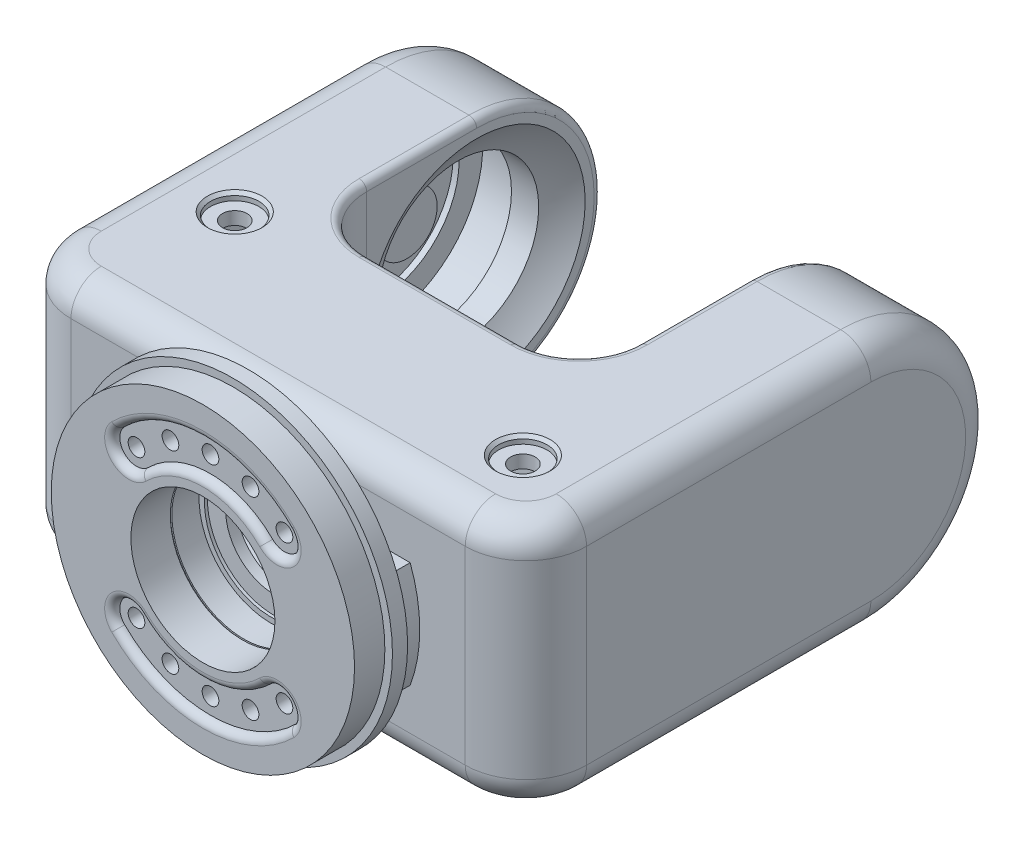
SolidWorks part; units mm, degrees
ref_plane "前视基准面" through (0, 0, 0) normal (0, 0, 1) x (1, 0, 0)
ref_plane "上视基准面" through (0, 0, 0) normal (0, 1, 0) x (1, 0, 0)
ref_plane "右视基准面" through (0, 0, 0) normal (1, 0, 0) x (0, 0, -1)
sketch "Sketch1" plane through (0, 0, 0) normal (0, 0, 1) x (1, 0, 0)
  circle A0 centre (0, 0) radius 100
  dimension "D1" = 200
extrude "Extrude1" add sketch "Sketch1" along normal mid plane 30
sketch "Sketch2" plane through (0, 0, 15) normal (0, 0, 1) x (1, 0, 0)
  line L0 (0, 0) -> (0, 100) construction
  line L1 (-48.7904, 48.7904) -> (0, 0) construction
  line L2 (0, 0) -> (100, 0) construction
  arc A0 (48.7904, 48.7904) -> (-48.7904, 48.7904) centre (0, 0) ccw construction
  arc A1 (56.5685, 56.5685) -> (-56.5685, 56.5685) centre (0, 0) ccw
  arc A2 (41.0122, 41.0122) -> (-41.0122, 41.0122) centre (0, 0) ccw
  arc A3 (41.0122, 41.0122) -> (56.5685, 56.5685) centre (48.7904, 48.7904) ccw
  arc A4 (-56.5685, 56.5685) -> (-41.0122, 41.0122) centre (-48.7904, 48.7904) ccw
  circle A5 centre (0, 0) radius 100 construction
  arc A6 (48.7904, -48.7904) -> (-48.7904, -48.7904) centre (0, 0) cw construction
  arc A7 (56.5685, -56.5685) -> (-56.5685, -56.5685) centre (0, 0) cw
  arc A8 (41.0122, -41.0122) -> (-41.0122, -41.0122) centre (0, 0) cw
  arc A9 (41.0122, -41.0122) -> (56.5685, -56.5685) centre (48.7904, -48.7904) cw
  arc A10 (-56.5685, -56.5685) -> (-41.0122, -41.0122) centre (-48.7904, -48.7904) cw
  point P4 (0, 69)
  point P18 (0, -69)
  point P23 (26.4052, 63.7477)
  point P24 (0, 69)
  point P25 (-26.4052, 63.7477)
  point P26 (26.4052, -63.7477)
  point P27 (0, -69)
  point P28 (-26.4052, -63.7477)
  dimension "D1" = 11
  dimension "D2" = 69
  dimension "D3" = 45
sketch "Sketch4" plane through (0, 0, -15) normal (0, 0, -1) x (-1, 0, 0)
  point P0 (48.7904, -48.7904)
  point P2 (26.4052, -63.7477)
  point P4 (0, -69)
  point P6 (-26.4052, -63.7477)
  point P8 (-48.7904, -48.7904)
  point P10 (48.7904, 48.7904)
  point P12 (26.4052, 63.7477)
  point P14 (0, 69)
  point P16 (-26.4052, 63.7477)
  point P18 (-48.7904, 48.7904)
hole_wizard "Ø11.0 (11) Diameter Hole3" positions "Sketch6" profile "Sketch7" hole size "Ø11.0" standard "GB" end condition through all
sketch "Sketch6" plane through (0, 0, -15) normal (0, 0, -1) x (-1, 0, 0)
  point P0 (-48.7904, 48.7904)
  point P3 (-26.4052, 63.7477)
  point P6 (0, 69)
  point P9 (26.4052, 63.7477)
  point P12 (48.7904, 48.7904)
  point P15 (48.7904, -48.7904)
  point P18 (26.4052, -63.7477)
  point P21 (0, -69)
  point P24 (-26.4052, -63.7477)
  point P27 (-48.7904, -48.7904)
sketch "Sketch7" plane through (48.7904, 48.7904, -15) normal (1, 0, 0) x (0, 1, 0)
  line L0 (0, 0) -> (0, 30)
  line L1 (0, 30) -> (5.5, 30)
  line L2 (5.5, 30) -> (5.5, 0)
  line L5 (5.5, 0) -> (0, 0)
  line L11 (0, -6.35) -> (0, 107.95) construction
  dimension "通孔孔直径" = 11
  dimension "通孔孔深度" = 30
extrude "Extrude2" cut sketch "Sketch2" against normal blind 5
sketch "Sketch8" plane through (0, 0, -15) normal (0, 0, -1) x (-1, 0, 0)
  line L0 (-64.8632, 46.8269) -> (-47.0259, 33.9495)
  line L1 (0, 0) -> (41.0122, 0) construction
  line L2 (0, 0) -> (0, 33.9495) construction
  line L3 (64.8632, 46.8269) -> (47.0259, 33.9495)
  line L4 (64.8632, -46.8269) -> (47.0259, -33.9495)
  line L5 (-64.8632, -46.8269) -> (-47.0259, -33.9495)
  circle A0 centre (-48.7904, -48.7904) radius 5.5 construction
  circle A1 centre (-26.4052, -63.7477) radius 5.5 construction
  circle A2 centre (0, -69) radius 5.5 construction
  circle A3 centre (26.4052, -63.7477) radius 5.5 construction
  arc A4 (-56.5685, 56.5685) -> (-41.0122, 41.0122) centre (-48.7904, 48.7904) ccw
  arc A5 (56.5685, 56.5685) -> (-56.5685, 56.5685) centre (0, 0) ccw
  arc A6 (41.0122, 41.0122) -> (56.5685, 56.5685) centre (48.7904, 48.7904) ccw
  arc A7 (41.0122, 41.0122) -> (-41.0122, 41.0122) centre (0, 0) ccw
  arc A8 (-56.5685, 56.5685) -> (-41.0122, 41.0122) centre (-48.7904, 48.7904) ccw construction
  arc A9 (56.5685, 56.5685) -> (-64.8632, 46.8269) centre (0, 0) ccw
  arc A10 (41.0122, 41.0122) -> (56.5685, 56.5685) centre (48.7904, 48.7904) ccw construction
  arc A11 (41.0122, 41.0122) -> (-47.0259, 33.9495) centre (0, 0) ccw
  arc A12 (-41.0122, -41.0122) -> (-56.5685, -56.5685) centre (-48.7904, -48.7904) ccw
  arc A13 (-41.0122, -41.0122) -> (41.0122, -41.0122) centre (0, 0) ccw
  arc A14 (56.5685, -56.5685) -> (41.0122, -41.0122) centre (48.7904, -48.7904) ccw
  arc A15 (-56.5685, -56.5685) -> (56.5685, -56.5685) centre (0, 0) ccw
  arc A16 (-41.0122, -41.0122) -> (-56.5685, -56.5685) centre (-48.7904, -48.7904) ccw construction
  arc A17 (-41.0122, -41.0122) -> (47.0259, -33.9495) centre (0, 0) ccw
  arc A18 (56.5685, -56.5685) -> (41.0122, -41.0122) centre (48.7904, -48.7904) ccw construction
  arc A19 (-56.5685, -56.5685) -> (64.8632, -46.8269) centre (0, 0) ccw
  circle A20 centre (48.7904, -48.7904) radius 5.5 construction
  circle A21 centre (48.7904, 48.7904) radius 5.5 construction
  circle A22 centre (26.4052, 63.7477) radius 5.5 construction
  circle A23 centre (0, 69) radius 5.5 construction
  circle A24 centre (-26.4052, 63.7477) radius 5.5 construction
  circle A25 centre (-48.7904, 48.7904) radius 5.5 construction
  circle A26 centre (-48.7904, -48.7904) radius 5.5
  circle A27 centre (-26.4052, -63.7477) radius 5.5
  circle A28 centre (0, -69) radius 5.5
  circle A29 centre (26.4052, -63.7477) radius 5.5
  circle A30 centre (48.7904, -48.7904) radius 5.5
  circle A31 centre (48.7904, 48.7904) radius 5.5
  circle A32 centre (26.4052, 63.7477) radius 5.5
  circle A33 centre (0, 69) radius 5.5
  circle A34 centre (-26.4052, 63.7477) radius 5.5
  circle A35 centre (-48.7904, 48.7904) radius 5.5
  arc A36 (-47.0259, -33.9495) -> (-41.0122, -41.0122) centre (0, 0) ccw
  arc A37 (-64.8632, -46.8269) -> (-56.5685, -56.5685) centre (0, 0) ccw
  arc A38 (47.0259, 33.9495) -> (41.0122, 41.0122) centre (0, 0) ccw
  arc A39 (64.8632, 46.8269) -> (56.5685, 56.5685) centre (0, 0) ccw
  dimension "D1" = 0
  dimension "D2" = 0
extrude "Extrude4" [suppressed] add sketch "Sketch8" along normal blind 5
fillet "Fillet1" radius 5 8 edges at (-56.5685, -41.0122, 15) (0, -80, 15) (56.5685, -41.0122, 15) (0, -58, 15) (0, 80, 15) (-56.5685, 41.0122, 15) (56.5685, 41.0122, 15) (0, 58, 15)
sketch "Sketch12" plane through (0, 0, -15) normal (0, 0, -1) x (-1, 0, 0)
  circle A0 centre (0, 0) radius 58
  dimension "D1" = 116
extrude "Extrude6" add sketch "Sketch12" along normal blind 23
sketch "Sketch15" plane through (0, 0, 0) normal (0, 1, 0) x (1, 0, 0)
  line L0 (0, -15) -> (0, 38) construction
  line L17 (-100, -15) -> (100, -15) construction
  line L18 (58, 38) -> (-58, 38) construction
  line L19 (0, 38) -> (32, 38)
  line L20 (32, 38) -> (32, 32)
  line L21 (32, 32) -> (44, 32)
  line L22 (44, 32) -> (44, 30)
  line L23 (44, 30) -> (47.5, 30)
  line L24 (47.5, 30) -> (47.5, 12)
  line L25 (47.5, 12) -> (48.5, 12)
  line L26 (48.5, 12) -> (48.5, 11)
  line L27 (48.5, 11) -> (47.5, 11)
  line L28 (47.5, 11) -> (47.5, -15)
  line L29 (47.5, -15) -> (0, -15)
  line L30 (0, 38) -> (0, -15)
  dimension "D1" = 95
  dimension "D2" = 97
  dimension "D3" = 64
  dimension "D4" = 88
  dimension "D5" = 2
  dimension "D6" = 1
  dimension "D7" = 18
  dimension "D8" = 6
revolve "Cut-Revolve1" cut sketch "Sketch15" angle 360 about L0
sketch "Sketch16" plane through (0, 0, -38) normal (0, 0, -1) x (-1, 0, 0)
  line L0 (0, 0) -> (100, 0) construction
  line L1 (-93.675, 35) -> (-46.2493, 35)
  line L2 (-93.675, -35) -> (-46.2493, -35)
  line L3 (46.2493, 35) -> (93.675, 35)
  line L4 (46.2493, -35) -> (93.675, -35)
  circle A0 centre (0, 0) radius 100 construction
  arc A1 (-93.675, 35) -> (-93.675, -35) centre (0, 0) ccw
  arc A2 (93.675, 35) -> (93.675, -35) centre (0, 0) cw
  arc A3 (-46.2493, 35) -> (-46.2493, -35) centre (0, 0) ccw
  circle A4 centre (0, 0) radius 58 construction
  arc A5 (46.2493, 35) -> (46.2493, -35) centre (0, 0) cw
  circle A6 centre (0, 0) radius 58 construction
  dimension "D3" = 100
  dimension "D4" = 100
  dimension "D5" = 58
  dimension "D6" = 58
  dimension "D1" = 35
  dimension "D2" = 35
extrude "Extrude7" add sketch "Sketch16" against normal up to next
sketch "Sketch20" plane through (0, 0, 0) normal (0, 1, 0) x (1, 0, 0)
  line L2 (-50, 143) -> (50, 143)
  line L3 (0, -15) -> (0, 38) construction
  line L4 (-100, -15) -> (100, -15) construction
  line L5 (-170, 68) -> (-170, 338)
  line L6 (-170, 338) -> (-90, 338)
  line L7 (-90, 338) -> (-90, 183)
  line L8 (90, 338) -> (90, 183)
  line L9 (170, 338) -> (90, 338)
  line L10 (170, 68) -> (170, 338)
  line L11 (-130, 28) -> (130, 28)
  line L12 (46.2493, 38) -> (-46.2493, 38) construction
  arc A0 (-50, 143) -> (-90, 183) centre (-50, 183) cw
  arc A1 (-130, 28) -> (-170, 68) centre (-130, 68) cw
  arc A2 (130, 28) -> (170, 68) centre (130, 68) ccw
  arc A3 (50, 143) -> (90, 183) centre (50, 183) ccw
  dimension "D2" = 40
  dimension "D1" = 10
  dimension "D3" = 340
  dimension "D4" = 180
extrude "Extrude12" add sketch "Sketch20" along normal mid plane 165
fillet "Fillet2" 2 edges at (130, 82.5, -338) (130, -82.5, -338) type full round first side face at (0, 82.5, -180.2386) second side face at (0, -82.5, -180.2386) middle face at (130, 0, -338)
fillet "Fillet3" 2 edges at (-130, -82.5, -338) (-130, 82.5, -338) type full round first side face at (0, -82.5, -166.4886) second side face at (0, 82.5, -166.4886) middle face at (-130, 0, -338)
sketch "Sketch21" plane through (0, 0, 0) normal (0, 1, 0) x (1, 0, 0)
  line L0 (-90, 255.5) -> (90, 255.5) construction
  line L1 (0, 370.5) -> (0, 153)
  line L2 (0, 153) -> (52.1416, 153)
  line L3 (50, 143) -> (-50, 143) construction
  arc A0 (52.1416, 153) -> (0, 370.5) centre (0, 255.5) ccw
  dimension "D1" = 230
  dimension "D2" = 10
revolve "Cut-Revolve2" cut sketch "Sketch21" angle 360 about L1
sketch "Sketch23" plane through (0, 0, 0) normal (0, 1, 0) x (1, 0, 0)
  line L0 (-155, 255.5) -> (-120, 255.5)
  line L1 (-120, 255.5) -> (-120, 168)
  line L2 (-80, 128) -> (80, 128)
  line L3 (120, 168) -> (120, 255.5)
  line L4 (120, 255.5) -> (155, 255.5)
  line L5 (155, 255.5) -> (155, 86)
  line L6 (115, 46) -> (-115, 46)
  line L7 (-155, 86) -> (-155, 255.5)
  line L9 (50, 143) -> (-50, 143) construction
  line L10 (170, 68) -> (170, 255.5) construction
  line L11 (-90, 255.5) -> (-170, 255.5) construction
  line L12 (-170, 255.5) -> (-170, 68) construction
  line L13 (93.675, 28) -> (46.2493, 28) construction
  arc A0 (-120, 168) -> (-80, 128) centre (-80, 168) ccw
  arc A1 (80, 128) -> (120, 168) centre (80, 168) ccw
  arc A2 (155, 86) -> (115, 46) centre (115, 86) cw
  arc A3 (-115, 46) -> (-155, 86) centre (-115, 86) cw
  arc A4 (90, 183.9109) -> (90, 327.0891) centre (0, 255.5) ccw construction
  arc A5 (50, 143) -> (90, 183) centre (50, 183) ccw construction
  arc A6 (-90, 327.0891) -> (-90, 183.9109) centre (0, 255.5) ccw construction
  arc A7 (-90, 183) -> (-50, 143) centre (-50, 183) ccw construction
  dimension "D6" = 40
  dimension "D1" = 18
  dimension "D2" = 15
  dimension "D3" = 15
  dimension "D4" = 15
  dimension "D5" = 5
  dimension "D7" = 5
extrude "Extrude13" cut sketch "Sketch23" against normal mid plane 138
fillet "Fillet4" radius 20 12 edges at (-158.2843, 82.5, -39.7157) (-170, 82.5, -161.75) (-170, 0, -338) (-170, -82.5, -161.75) (-158.2843, -82.5, -39.7157) (158.2843, -82.5, -39.7157) (170, -82.5, -161.75) (170, 0, -338) (170, 82.5, -161.75) (158.2843, 82.5, -39.7157) (0, -82.5, -28) (0, 82.5, -28)
sketch "Sketch24" plane through (0, 0, 0) normal (1, 0, 0) x (0, 0, -1)
  circle A0 centre (255.5, 0) radius 53
  dimension "D1" = 106
extrude "Extrude14" cut sketch "Sketch24" against normal mid plane 310
sketch "Sketch27" plane through (-155, 0, 0) normal (1, 0, 0) x (0, 0, -1)
  line L0 (255.5, 69) -> (86, 69) construction
  circle A0 centre (255.5, 0) radius 69
extrude "Extrude16" cut sketch "Sketch27" along normal up to surface (35 mm away) up to face at (-120, 0, -217.5)
sketch "Sketch28" plane through (155, 0, 0) normal (-1, 0, 0) x (0, 0, 1)
  line L0 (-86, -69) -> (-255.5, -69) construction
  circle A0 centre (-255.5, 0) radius 69
extrude "Extrude17" cut sketch "Sketch28" along normal up to surface (35 mm away) up to face at (120, 0, -217.5)
sketch "Sketch29" plane through (0, 0, 0) normal (0, 1, 0) x (1, 0, 0)
  line L0 (0, -15) -> (0, 28) construction
  line L1 (-100, -15) -> (100, -15) construction
  line L2 (-46.2493, 28) -> (46.2493, 28) construction
  line L7 (0, 28) -> (47.5, 28)
  line L8 (47.5, 28) -> (47.5, 30)
  line L9 (47.5, 30) -> (44, 30)
  line L11 (44, 30) -> (44, 32)
  line L12 (44, 32) -> (32, 32)
  line L14 (32, 32) -> (32, 39)
  line L15 (32, 39) -> (53.5, 39)
  line L16 (53.5, 39) -> (53.5, 127)
  line L18 (53.5, 127) -> (34.5, 127)
  line L19 (34.5, 127) -> (34.5, 143)
  line L22 (50, 143) -> (-50, 143) construction
  line L24 (0, 143) -> (0, 28)
  line L25 (0, 143) -> (34.5, 143)
  dimension "D1" = 95
  dimension "D2" = 2
  dimension "D3" = 2
  dimension "D4" = 88
  dimension "D5" = 64
  dimension "D6" = 7
  dimension "D7" = 107
  dimension "D8" = 69
  dimension "D9" = 16
revolve "Cut-Revolve3" cut sketch "Sketch29" angle 360 about L0
sketch "Sketch30" plane through (-155, 0, 0) normal (1, 0, 0) x (0, 0, -1)
  circle A0 centre (255.5, 0) radius 53.5
  dimension "D1" = 107
extrude "Extrude18" cut sketch "Sketch30" against normal blind 4
mirror "Mirror1" about plane through (0, 0, 0) normal (1, 0, 0) of "Extrude18"
sketch "Sketch33" plane through (0, 0, 0) normal (0, 1, 0) x (1, 0, 0)
  line L0 (170, 255.5) -> (200.3092, 255.5) construction
  line L1 (159, 255.5) -> (159, 278)
  line L2 (90, 255.5) -> (150, 255.5) construction
  line L3 (159, 278) -> (151, 278)
  line L4 (151, 278) -> (151, 275.5)
  line L5 (151, 275.5) -> (136, 275.5)
  line L6 (136, 275.5) -> (136, 255.5)
  line L7 (136, 255.5) -> (159, 255.5)
  line L8 (159, 309) -> (159, 202) construction
  dimension "D1" = 45
  dimension "D2" = 40
  dimension "D3" = 8
  dimension "D4" = 15
revolve "Revolve1" add sketch "Sketch33" angle 360 about L0
mirror "Mirror2" about plane through (0, 0, 0) normal (1, 0, 0) of "Revolve1"
fillet "Fillet5" radius 8 2 edges at (-159, 0, -233) (159, 0, -233)
sketch "Sketch34" plane through (0, 69, 0) normal (0, -1, 0) x (1, 0, 0)
  line L0 (-120, -168) -> (-120, -255.5) construction
  line L1 (80, -128) -> (-80, -128) construction
  line L6 (120, -255.5) -> (120, -168) construction
  circle A0 centre (-117, -123) radius 18 construction
  circle A1 centre (117, -79) radius 18 construction
  circle A2 centre (-117, -123) radius 24 construction
  circle A3 centre (117, -79) radius 24 construction
  circle A4 centre (-117, -123) radius 26
  dimension "D3" = 36
  dimension "D4" = 15
  dimension "D5" = 67
  dimension "D6" = 36
  dimension "D7" = 48
  dimension "D8" = 48
  dimension "D9" = 52
  dimension "D1" = 15
  dimension "D2" = 23
extrude "Extrude19" cut sketch "Sketch34" along normal up to surface (138 mm away) up to face at (0, -69, -153.7386)
sketch "Sketch35" plane through (0, -82.5, 0) normal (0, -1, 0) x (1, 0, 0)
  circle A0 centre (-117, -123) radius 16
  circle A1 centre (117, -79) radius 16
  dimension "D1" = 32
  dimension "D2" = 32
extrude "Extrude21" cut sketch "Sketch35" against normal blind 5
mirror "Mirror5" about plane through (0, 0, 0) normal (0, 1, 0) of "Extrude21"
chamfer "Chamfer2" distance 2 angle 45 4 edges at (117, 82.5, -95) (-117, 82.5, -139) (117, -82.5, -95) (-117, -82.5, -139)
sketch "Sketch36" plane through (0, 0, 0) normal (0, 1, 0) x (1, 0, 0)
  circle A0 centre (-117, 123) radius 8.1
  circle A1 centre (117, 79) radius 8.1
  dimension "D1" = 16.2
extrude "Extrude22" cut sketch "Sketch36" along normal through all both and the other way through all
fillet "Fillet6" radius 5 12 edges at (-78.2843, 82.5, -154.7157) (0, 82.5, -143) (78.2843, 82.5, -154.7157) (90, 82.5, -219.25) (90, 0, -338) (90, -82.5, -219.25) (78.2843, -82.5, -154.7157) (0, -82.5, -143) (-78.2843, -82.5, -154.7157) (-90, -82.5, -219.25) (-90, 0, -338) (-90, 82.5, -219.25)
sketch "Sketch37" plane through (0, 0, -15) normal (0, 0, -1) x (-1, 0, 0)
  circle A0 centre (0, 0) radius 100
  circle A1 centre (0, 0) radius 105
  dimension "D1" = 200
  dimension "D2" = 210
extrude "Extrude23" add sketch "Sketch37" against normal blind 10
